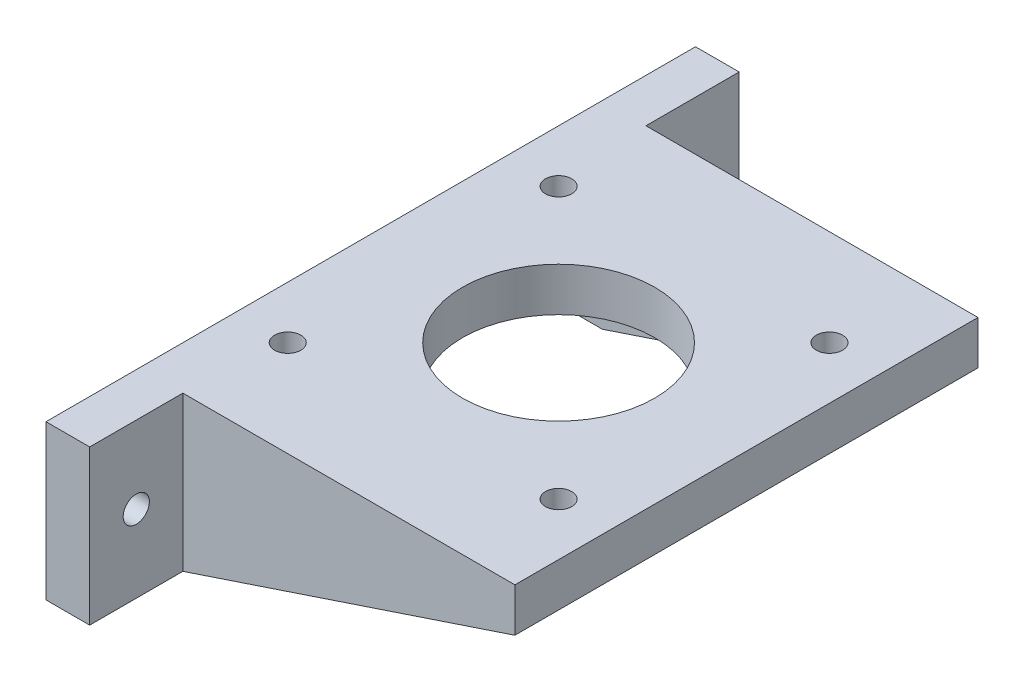
SolidWorks part; units mm, degrees
material "ABS"
ref_plane "Front Plane" through (0, 0, 0) normal (0, 0, 1) x (1, 0, 0)
ref_plane "Top Plane" through (0, 0, 0) normal (0, 1, 0) x (1, 0, 0)
ref_plane "Right Plane" through (0, 0, 0) normal (1, 0, 0) x (0, 0, -1)
sketch "Sketch1" plane through (0, 0, 0) normal (0, 0, 1) x (1, 0, 0)
  line L0 (5, 5) -> (43, 5)
  line L1 (0, 0) -> (5, 0)
  line L2 (0, 0) -> (0, 5)
  line L3 (0, 5) -> (5, 5)
  line L4 (5, 0) -> (5, 5)
  line L5 (43, 5) -> (43, 0)
  line L6 (43, 0) -> (5, 0)
  line L7 (5, 0) -> (5, -12.666)
  line L8 (5, -12.666) -> (0, -12.666)
  line L9 (0, -12.666) -> (0, 0)
  line L10 (5, -12.666) -> (43, 0)
  dimension "D1" = 5
  dimension "D2" = 5
  dimension "D3" = 43
  dimension "D4" = 12.666
extrude "Boss-Extrude1" add sketch "Sketch1" against normal blind 43 contours L1 L4 L3 L2 | L6 L5 L0 L4 region at (2.5, 2.5, 0) region at (24, 2.5, 0)
sketch "Sketch2" plane through (0, 5, 0) normal (0, 1, 0) x (1, 0, 0)
  line L3 (0, 43) -> (0, 0) construction
  line L4 (0, 0) -> (43, 0) construction
  circle A0 centre (21.5, 21.5) radius 11
  circle A1 centre (37, 37) radius 1.5
  circle A2 centre (6, 37) radius 1.5
  circle A3 centre (6, 6) radius 1.5
  circle A4 centre (37, 6) radius 1.5
  dimension "D3" = 22
  dimension "D4" = 3
  dimension "D1" = 21.5
  dimension "D2" = 21.5
  dimension "D5" = 15.5
  dimension "D6" = 15.5
  dimension "D7" = 2
  dimension "D8" = 2
extrude "Cut-Extrude1" cut sketch "Sketch2" against normal through all
extrude "Boss-Extrude2" add sketch "Sketch1<3>" along normal blind 5 contours L7 L10 L6 | L6 L5 L0 L4 | L1 L4 L3 L2 | L9 L8 L7 L1 region at (2.5, 2.5, 0) region at (24, 2.5, 0) region at (2.5, -6.333, 0) region at (17.6667, -4.222, 0)
sketch "Sketch1<3>" plane through (0, 0, 0) normal (0, 0, 1) x (1, 0, 0) same geometry as "Sketch1"
extrude "Boss-Extrude3" add sketch "Sketch1<4>" against normal blind 5 from vertex contours L1 L4 L3 L2 | L9 L8 L7 L1 | L7 L10 L6 | L6 L5 L0 L4 region at (2.5, 2.5, 0) region at (24, 2.5, 0) region at (2.5, -6.333, 0) region at (17.6667, -4.222, 0) starting at point (0, 5, -43)
sketch "Sketch1<4>" plane through (0, 0, 0) normal (0, 0, 1) x (1, 0, 0) same geometry as "Sketch1"
sketch "Sketch3" plane through (0, 0, 0) normal (-1, 0, 0) x (0, 0, 1)
  line L0 (5, -12.666) -> (0, -12.666) construction
  line L1 (5, 5) -> (15.666, 5)
  line L2 (5, 5) -> (5, -12.666)
  line L3 (5, -12.666) -> (15.666, -12.666)
  line L4 (15.666, 5) -> (15.666, -12.666)
  line L5 (10.333, 5) -> (10.333, -12.666) construction
  line L6 (15.666, -3.833) -> (5, -3.833) construction
  line L7 (-21.5, 5) -> (-21.5, 0) construction
  line L8 (-48, 5) -> (5, 5) construction
  line L9 (-43, 0) -> (0, 0) construction
  line L10 (-48, -12.666) -> (-58.666, -12.666)
  line L11 (-58.666, 5) -> (-58.666, -12.666)
  line L12 (-53.333, 5) -> (-53.333, -12.666) construction
  line L13 (-58.666, -3.833) -> (-48, -3.833) construction
  line L14 (-48, 5) -> (-48, -12.666)
  line L15 (-48, 5) -> (-58.666, 5)
  circle A0 centre (10.333, -3.833) radius 1.5
  circle A1 centre (-53.333, -3.833) radius 1.5
  dimension "D2" = 3
  dimension "D1" = 10.666
extrude "Boss-Extrude4" add sketch "Sketch3" against normal blind 5
equation "\"rod_diameter\"= 8"
equation "\"rod_hole_thickness\"= 4"
equation "\"rod_radius\"= \"rod_diameter\" / 2"
equation "\"platter_diameter\"= 320"
equation "\"platter_radius\"= \"platter_diameter\" / 2"
equation "\"extruder_mount_hole_spacing\"= 75"
equation "\"arm_rod_spacing\"= 40"
equation "\"D2@Sketch2\" = \"D1@Boss-Extrude1\" / 2"
equation "\"motor_level_rod_spacing\"= 15"
equation "\"top_frame_spacing\"= 90"
equation "\"linear_bearing_diameter\"= 15"
equation "\"z_rod_spacing\"= 75"
equation "\"platter_rod_spacing\"= 50"
equation "\"rod_nut_thickness\"= 6.5"
equation "\"rod_nut_inscribed_diameter\"= 13"
equation "\"z_height\"= 350"
equation "\"gear_pitch\"=2"
equation "\"r_gear_teeth\"= 450"
equation "\"theta_gear_teeth\"= 385"
equation "\"sheet_thickness\"=5.333"
equation "\"sheet_tab_hole_thickness\"= \"sheet_thickness\""
equation "\"sheet_tab_width\"= \"sheet_thickness\"*2"
equation "\"sheet_bolt_diameter\"= 3"
equation "\"sheet_bolt_length\"= 16"
equation "\"sheet_nut_diameter\"= 5.5"
equation "\"sheet_nut_thickness\"= 2.5"
equation "\"sheet_nut_depth\"= 10"
equation "\"bearing_outside_diameter\"= 22"
equation "\"bearing_thickness\"= 7"
equation "\"corner_part_thickness\"= \"sheet_thickness\" + \"bearing_thickness\""
equation "\"D4@Sketch1\"=\"sheet_thickness\"*2+7-\"D1@Sketch1\""
equation "\"D1@Sketch2\"= \"D3@Sketch1\" / 2"
equation "\"D1@Sketch3\"=\"sheet_thickness\"*2"
equation "\"D2@Sketch3\"=\"sheet_bolt_diameter\""
